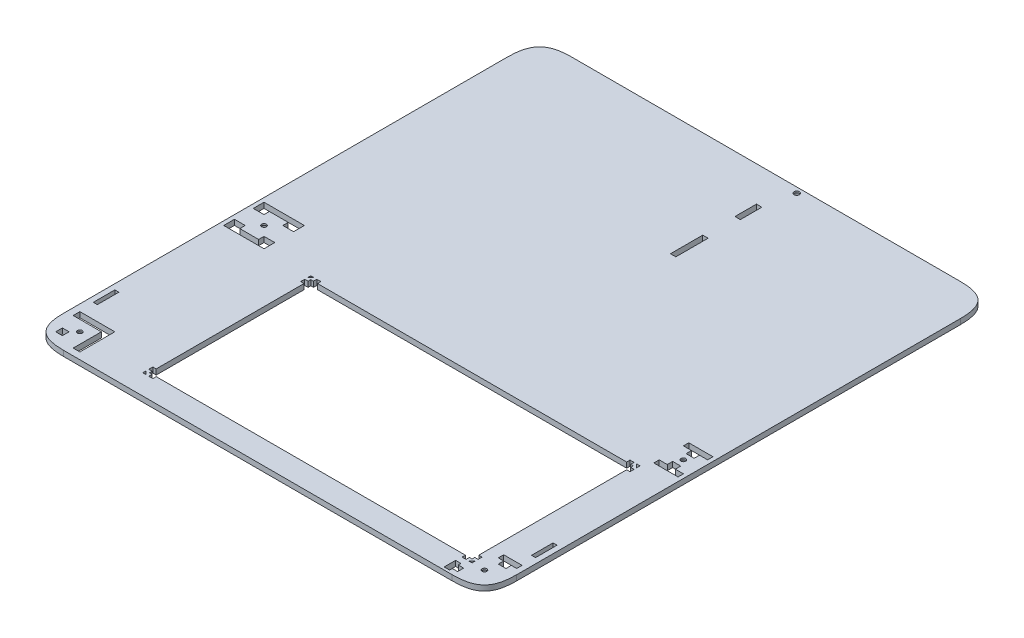
SolidWorks part; units mm, degrees
ref_plane "Front Plane" through (0, 0, 0) normal (0, 0, 1) x (1, 0, 0)
ref_plane "Top Plane" through (0, 0, 0) normal (0, 1, 0) x (1, 0, 0)
ref_plane "Right Plane" through (0, 0, 0) normal (1, 0, 0) x (0, 0, -1)
sketch "Sketch1" plane through (0, 0, 0) normal (0, 1, 0) x (1, 0, 0)
  line L1 (0, 0) -> (337, 0)
  line L2 (0, 0) -> (0, 377.97)
  line L3 (0, 377.97) -> (337, 377.97)
  line L4 (337, 0) -> (337, 377.97)
  line L5 (70.28, 137.5) -> (310.28, 137.5)
  line L6 (70.28, 137.5) -> (70.28, 17.5)
  line L7 (70.28, 17.5) -> (310.28, 17.5)
  line L8 (310.28, 137.5) -> (310.28, 17.5)
  dimension "D1" = 337
  dimension "D2" = 377.97
  dimension "D3" = 240
  dimension "D4" = 120
  dimension "D5" = 17.5
  dimension "D6" = 26.72
extrude "Boss-Extrude1" add sketch "Sketch1" against normal blind 4
fillet "Fillet1" radius 24 4 edges at (0, -2, 0) (337, -2, 0) (0, -2, -377.97) (337, -2, -377.97) conic rho 0.55
sketch "Sketch3" plane through (0, 0, 0) normal (0, 1, 0) x (1, 0, 0)
  line L0 (337, 24) -> (337, 353.97) construction
  line L1 (24, 0) -> (313, 0) construction
  line L2 (0, 353.97) -> (0, 24) construction
  line L3 (309, 4) -> (309, 2)
  line L4 (305, 10.5) -> (309, 10.5)
  line L5 (305, 10.5) -> (305, 2)
  line L6 (305, 2) -> (309, 2)
  line L7 (309, 10.5) -> (309, 8.5)
  line L8 (309, 8.5) -> (313, 8.5)
  line L10 (309, 4) -> (313, 4)
  line L11 (313, 8.5) -> (313, 4)
  line L12 (329, 28) -> (333, 28)
  line L13 (319.28, 32) -> (333, 32)
  line L14 (319.28, 32) -> (319.28, 28)
  line L15 (319.28, 28) -> (323.28, 28)
  line L16 (333, 32) -> (333, 28)
  line L18 (323.28, 28) -> (323.28, 24)
  line L19 (323.28, 24) -> (329, 24)
  line L20 (329, 28) -> (329, 24)
  line L21 (328, 151) -> (334, 151)
  line L30 (26, 5) -> (31, 5)
  line L36 (26, 5) -> (26, 26)
  line L37 (9, 14) -> (14, 14)
  line L38 (9, 14) -> (9, 9)
  line L39 (9, 9) -> (14, 9)
  line L40 (14, 14) -> (14, 9)
  line L41 (26, 31) -> (31, 31)
  line L42 (31, 5) -> (31, 31)
  line L43 (26, 31) -> (5, 31)
  line L45 (26, 26) -> (5, 26)
  line L46 (5, 31) -> (5, 26)
  line L47 (3, 140) -> (33, 140)
  line L48 (3, 140) -> (3, 144)
  line L49 (11, 144) -> (25, 144)
  line L50 (33, 140) -> (33, 144)
  line L52 (3, 144) -> (3, 148)
  line L53 (3, 148) -> (11, 148)
  line L54 (11, 144) -> (11, 148)
  line L56 (33, 144) -> (33, 148)
  line L57 (33, 148) -> (25, 148)
  line L58 (25, 144) -> (25, 148)
  line L59 (3, 170) -> (33, 170)
  line L60 (3, 170) -> (3, 166)
  line L61 (11, 166) -> (25, 166)
  line L62 (33, 170) -> (33, 166)
  line L64 (3, 166) -> (3, 162)
  line L65 (3, 162) -> (11, 162)
  line L66 (11, 166) -> (11, 162)
  line L68 (33, 166) -> (33, 162)
  line L69 (33, 162) -> (25, 162)
  line L70 (25, 166) -> (25, 162)
  line L71 (316, 147) -> (334, 147)
  line L72 (316, 147) -> (316, 151)
  line L73 (316, 151) -> (322, 151)
  line L74 (334, 147) -> (334, 151)
  line L76 (322, 151) -> (322, 155)
  line L77 (322, 155) -> (328, 155)
  line L78 (328, 151) -> (328, 155)
  line L79 (328, 169) -> (334, 169)
  line L80 (316, 173) -> (334, 173)
  line L81 (316, 173) -> (316, 169)
  line L82 (316, 169) -> (322, 169)
  line L83 (334, 173) -> (334, 169)
  line L85 (322, 169) -> (322, 165)
  line L86 (322, 165) -> (328, 165)
  line L87 (328, 169) -> (328, 165)
  line L88 (313, 377.97) -> (24, 377.97) construction
  line L89 (333, 42) -> (330, 42)
  line L90 (333, 42) -> (333, 58)
  line L91 (333, 58) -> (330, 58)
  line L92 (330, 42) -> (330, 58)
  line L93 (4, 42) -> (7, 42)
  line L94 (4, 42) -> (4, 58)
  line L95 (4, 58) -> (7, 58)
  line L96 (7, 42) -> (7, 58)
  line L97 (187.4, 351.97) -> (191.4, 351.97)
  line L98 (187.4, 351.97) -> (187.4, 335.97)
  line L99 (187.4, 335.97) -> (191.4, 335.97)
  line L100 (191.4, 351.97) -> (191.4, 335.97)
  line L102 (187.4, 311.97) -> (191.4, 311.97)
  line L103 (187.4, 311.97) -> (187.4, 287.97)
  line L104 (187.4, 287.97) -> (191.4, 287.97)
  line L105 (191.4, 311.97) -> (191.4, 287.97)
  circle A0 centre (322, 15) radius 1.75
  circle A1 centre (18, 18) radius 1.75
  circle A2 centre (18, 155) radius 1.75
  circle A3 centre (325, 160) radius 1.75
  circle A4 centre (195.4, 373.97) radius 2
  point P37 (5, 28.5)
  dimension "D3" = 3.5
  dimension "D6" = 3.5
  dimension "D45" = 3.5
  dimension "D62" = 3.5
  dimension "D79" = 4
  dimension "D80" = 4
  dimension "D81" = 4
  dimension "D1" = 15
  dimension "D2" = 15
  dimension "D4" = 18
  dimension "D5" = 18
  dimension "D7" = 24
  dimension "D8" = 4
  dimension "D9" = 2
  dimension "D10" = 2
  dimension "D11" = 4.5
  dimension "D12" = 2
  dimension "D13" = 4
  dimension "D14" = 4
  dimension "D15" = 13.72
  dimension "D16" = 4
  dimension "D17" = 4
  dimension "D18" = 4
  dimension "D19" = 4
  dimension "D20" = 24
  dimension "D21" = 5
  dimension "D22" = 5
  dimension "D23" = 9
  dimension "D24" = 9
  dimension "D25" = 26
  dimension "D26" = 5
  dimension "D27" = 5
  dimension "D28" = 5
  dimension "D29" = 21
  dimension "D30" = 5
  dimension "D31" = 30
  dimension "D32" = 4
  dimension "D33" = 4
  dimension "D34" = 8
  dimension "D35" = 8
  dimension "D36" = 4
  dimension "D37" = 30
  dimension "D38" = 4
  dimension "D39" = 4
  dimension "D40" = 4
  dimension "D41" = 30
  dimension "D42" = 140
  dimension "D43" = 3
  dimension "D44" = 3
  dimension "D46" = 11
  dimension "D47" = 4
  dimension "D48" = 4
  dimension "D49" = 4
  dimension "D50" = 18
  dimension "D51" = 3
  dimension "D52" = 6
  dimension "D53" = 6
  dimension "D54" = 4
  dimension "D55" = 4
  dimension "D56" = 4
  dimension "D57" = 18
  dimension "D58" = 6
  dimension "D59" = 6
  dimension "D60" = 10
  dimension "D61" = 147
  dimension "D63" = 5
  dimension "D64" = 9
  dimension "D65" = 3
  dimension "D66" = 16
  dimension "D67" = 10
  dimension "D68" = 4
  dimension "D69" = 4
  dimension "D70" = 16
  dimension "D71" = 3
  dimension "D72" = 0
  dimension "D73" = 145.6
  dimension "D74" = 26
  dimension "D75" = 4
  dimension "D76" = 16
  dimension "D77" = 24
  dimension "D78" = 24
extrude "Cut-Extrude1" cut sketch "Sketch3" against normal up to next
ref_plane "Plane3" through (190.28, 0, 0) normal (-1, 0, 0) x (0, 0, 1)
ref_plane "Plane6" through (0, 0, -77.5) normal (0, 0, 1) x (1, 0, 0)
sketch "Sketch5" plane through (0, 0, 0) normal (0, 1, 0) x (1, 0, 0)
  line L0 (310.28, 17.5) -> (310.28, 137.5) construction
  line L3 (310.28, 15) -> (312.78, 15)
  line L4 (312.78, 17.5) -> (312.78, 15)
  line L5 (310.28, 22.5) -> (312.78, 22.5)
  line L6 (310.28, 22.5) -> (310.28, 19.5)
  line L7 (310.28, 19.5) -> (312.78, 19.5)
  line L8 (312.78, 22.5) -> (312.78, 19.5)
  line L9 (70.28, 17.5) -> (310.28, 17.5) construction
  line L10 (305.28, 17.5) -> (308.28, 17.5)
  line L11 (305.28, 17.5) -> (305.28, 15)
  line L12 (305.28, 15) -> (308.28, 15)
  line L13 (308.28, 17.5) -> (308.28, 15)
  line L14 (310.28, 15) -> (312.78, 17.5)
  dimension "D1" = 2.5
  dimension "D2" = 2.5
  dimension "D4" = 3
  dimension "D6" = 3
extrude "Cut-Extrude2" cut sketch "Sketch5" against normal up to next
mirror "Mirror1" about plane through (0, 0, -77.5) normal (0, 0, 1) of "Cut-Extrude2" second plane through (190.28, 0, 0) second plane normal (-1, 0, 0)
sketch "Sketch6" plane through (0, -4, 0) normal (0, -1, 0) x (1, 0, 0)
  circle A0 centre (18, -155) radius 3.5
  circle A1 centre (18, -18) radius 3.5
  circle A2 centre (322, -15) radius 3.5
  circle A3 centre (325, -160) radius 3.5
  circle A4 centre (195.4, -373.97) radius 3.5
  dimension "D1" = 7
  dimension "D2" = 7
  dimension "D3" = 7
  dimension "D4" = 7
  dimension "D5" = 7
extrude "Cut-Extrude3" cut sketch "Sketch6" against normal blind 2.8
